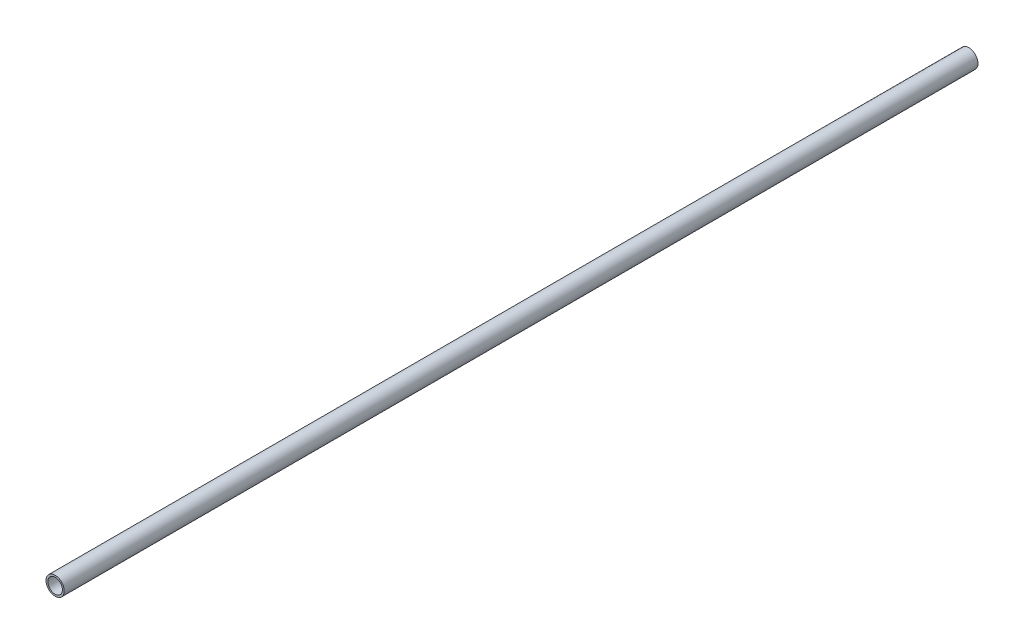
SolidWorks part; units mm, degrees
ref_plane "Front Plane" through (0, 0, 0) normal (0, 0, 1) x (1, 0, 0)
ref_plane "Top Plane" through (0, 0, 0) normal (0, 1, 0) x (1, 0, 0)
ref_plane "Right Plane" through (0, 0, 0) normal (1, 0, 0) x (0, 0, -1)
sketch "Sketch1" plane through (0, 0, 0) normal (0, 0, 1) x (1, 0, 0)
  circle A0 centre (0, 0) radius 5
  circle A1 centre (0, 0) radius 4
  dimension "D1" = 8
  dimension "D2" = 10
extrude "Boss-Extrude1" add sketch "Sketch1" along normal blind 500 contours A0 A1 region at (-4.8586, 0, 0)
